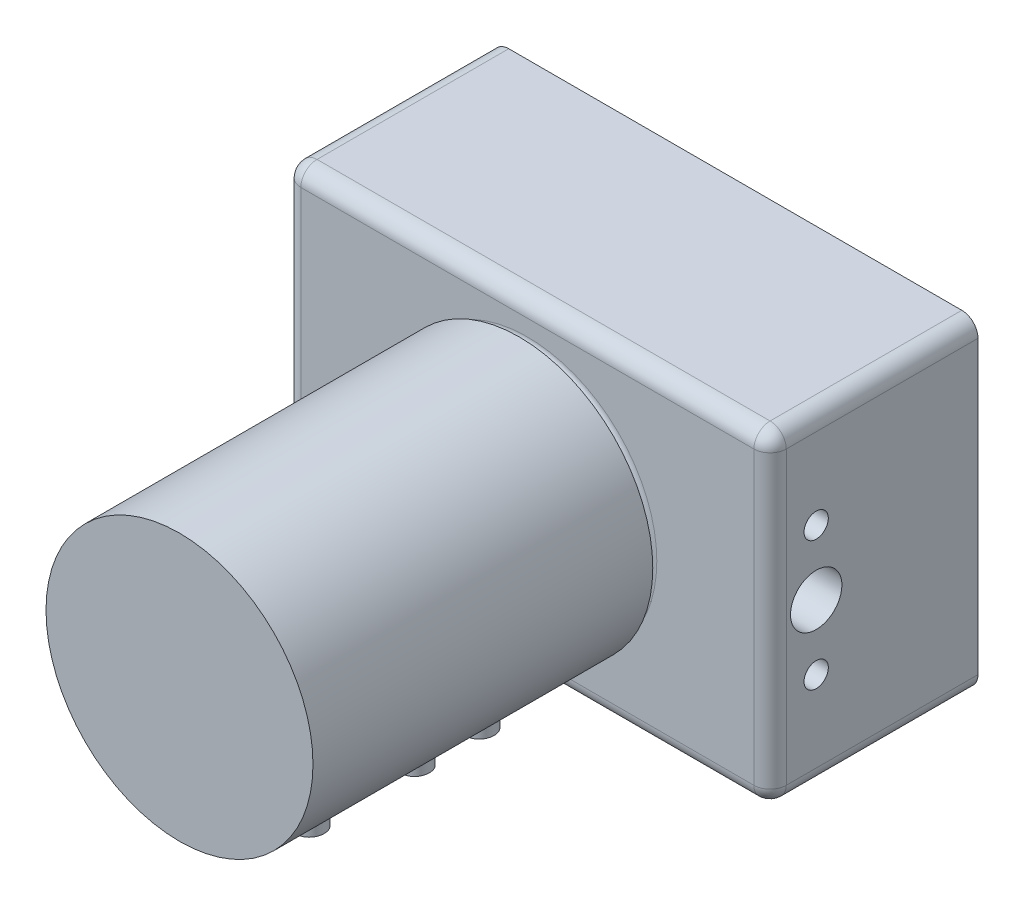
SolidWorks part; units mm, degrees
ref_plane "Front Plane" through (0, 0, 0) normal (0, 0, 1) x (1, 0, 0)
ref_plane "Top Plane" through (0, 0, 0) normal (0, 1, 0) x (1, 0, 0)
ref_plane "Right Plane" through (0, 0, 0) normal (1, 0, 0) x (0, 0, -1)
sketch "Sketch1" plane through (0, 0, 0) normal (0, 0, 1) x (1, 0, 0)
  line L1 (-28, 20) -> (28, 20)
  line L2 (-30, 18) -> (-30, -18)
  line L3 (-28, -20) -> (28, -20)
  line L4 (30, 18) -> (30, -18)
  line L5 (-30, 20) -> (30, -20) construction
  line L6 (-30, -20) -> (30, 20) construction
  arc A0 (-30, -18) -> (-28, -20) centre (-28, -18) ccw
  arc A1 (28, -20) -> (30, -18) centre (28, -18) ccw
  arc A2 (28, 20) -> (30, 18) centre (28, 18) cw
  arc A3 (-28, 20) -> (-30, 18) centre (-28, 18) ccw
  point P1 (0, 0)
  dimension "D3" = 2
  dimension "D1" = 60
  dimension "D2" = 40
extrude "Boss-Extrude1" add sketch "Sketch1" along normal blind 25.7
sketch "Sketch2" plane through (0, 0, 25.7) normal (0, 0, 1) x (1, 0, 0)
  circle A0 centre (0, 0) radius 15
  dimension "D1" = 30
extrude "Boss-Extrude2" add sketch "Sketch2" along normal blind 1
fillet "Fillet1" radius 1 1 edges at (15, 0, 25.7)
fillet "Fillet2" radius 2 8 edges at (29.4142, 19.4142, 25.7) (30, 0, 25.7) (29.4142, -19.4142, 25.7) (0, -20, 25.7) (-29.4142, -19.4142, 25.7) (-30, 0, 25.7) (-29.4142, 19.4142, 25.7) (0, 20, 25.7)
sketch "Sketch3" plane through (0, 0, 26.7) normal (0, 0, 1) x (1, 0, 0)
  circle A0 centre (0, 0) radius 16.5
  dimension "D1" = 33
extrude "Boss-Extrude3" add sketch "Sketch3" along normal blind 42
sketch "Sketch4" plane through (0, -20, 0) normal (0, -1, 0) x (1, 0, 0)
  line L0 (0, 0) -> (0, -4.6153) construction
  circle A0 centre (0, 20) radius 3.175
  circle A1 centre (-8, 20) radius 1.5
  circle A2 centre (8, 20) radius 1.5
  point P7 (0, 0)
  dimension "D1" = 20
  dimension "D2" = 6.35
  dimension "D3" = 8
  dimension "D4" = 3
extrude "Cut-Extrude1" cut sketch "Sketch4" against normal blind 5
sketch "Sketch5" plane through (0, 0, 0) normal (0, 1, 0) x (1, 0, 0)
  circle A0 centre (0, -31.5) radius 1.7
  circle A1 centre (0, -39.5) radius 1.7
  circle A2 centre (0, -52.5) radius 1.7
  point P6 (0, 0)
  point P8 (0, 0)
  point P9 (0, 0)
  dimension "D1" = 31.5
  dimension "D2" = 3.4
  dimension "D3" = 8
  dimension "D4" = 13
extrude "Boss-Extrude4" add sketch "Sketch5" along direction (0, -1, 0) on the side against the normal offset from surface (23 mm away) 6.5
sketch "Sketch6" plane through (30, 0, 0) normal (1, 0, 0) x (0, 0, -1)
  line L0 (0, 0) -> (-20, 0) construction
  circle A0 centre (-20, 0) radius 3.175
  circle A1 centre (-20, -8) radius 1.5
  circle A2 centre (-20, 8) radius 1.5
  dimension "D1" = 6.35
  dimension "D3" = 8
  dimension "D4" = 3
  dimension "D2" = 20
extrude "Cut-Extrude2" cut sketch "Sketch6" against normal blind 5
mirror "Mirror1" about plane through (0, 0, 0) normal (1, 0, 0) of "Cut-Extrude2"
